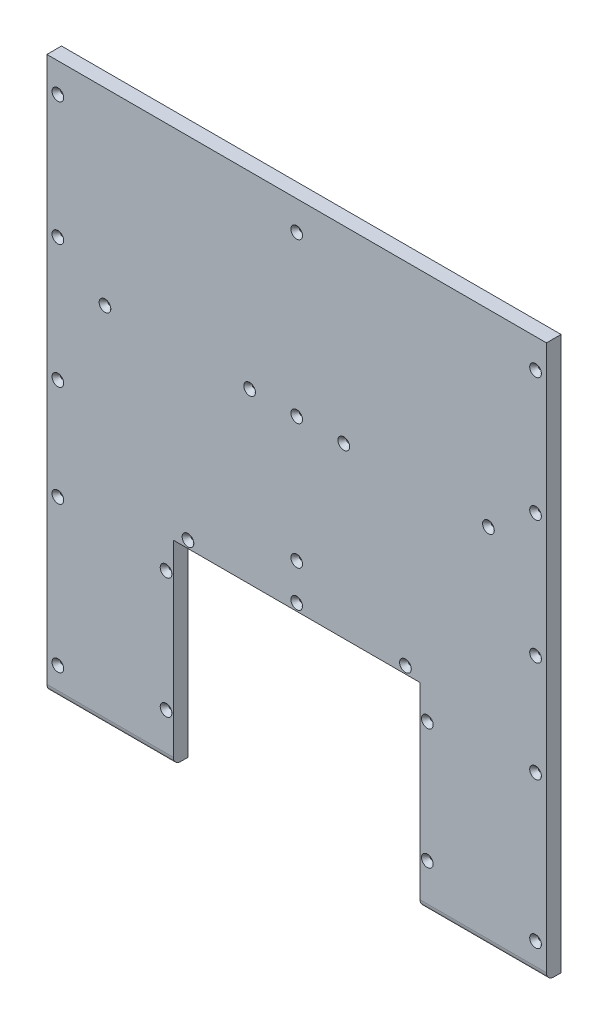
SolidWorks part; units mm, degrees
material "Beech"
ref_plane "Front Plane" through (0, 0, 0) normal (0, 0, 1) x (1, 0, 0)
ref_plane "Top Plane" through (0, 0, 0) normal (0, 1, 0) x (1, 0, 0)
ref_plane "Right Plane" through (0, 0, 0) normal (1, 0, 0) x (0, 0, -1)
sketch "Sketch1" plane through (0, 0, 0) normal (0, 0, 1) x (1, 0, 0)
  line L0 (124.0045, -60.2629) -> (124.0045, 250.6666) construction
  line L1 (16.7045, -230.2629) -> (-93.2955, -230.2629)
  line L2 (16.7045, -60.2629) -> (16.7045, -230.2629)
  line L3 (-93.2955, -230.2629) -> (-93.2955, 250.6666)
  line L16 (341.3045, -230.2629) -> (341.3045, 250.6666)
  line L17 (341.3045, 250.6666) -> (-93.2955, 250.6666)
  line L21 (16.7045, -60.2629) -> (231.3045, -60.2629)
  line L22 (231.3045, -60.2629) -> (231.3045, -230.2629)
  line L23 (231.3045, -230.2629) -> (341.3045, -230.2629)
  dimension "D1" = 434.6
  dimension "D2" = 480.9295
  dimension "D3" = 110
  dimension "D4" = 170
extrude "Boss-Extrude1" add sketch "Sketch1" against normal blind 12.7
fillet "Fillet1" radius 6.35 2 edges at (286.3045, -230.2629, 0) (-38.2955, -230.2629, 0)
hole_wizard "Hole1" positions "Sketch2" profile "Sketch3" legacy end condition through all
sketch "Sketch2" plane through (0, 0, 0) normal (0, 0, 1) x (1, 0, 0)
  line L8 (331.7795, 250.6666) -> (331.7795, -230.2629) construction
  line L9 (341.3045, 250.6666) -> (-93.2955, 250.6666) construction
  line L12 (322.2545, 226.323) -> (322.2545, -204.8629) construction
  line L13 (341.3045, -204.8629) -> (341.3045, 226.323) construction
  line L15 (331.7795, 225.2666) -> (331.7795, 10.2019)
  line L16 (331.7795, 10.2019) -> (331.7795, -204.8629)
  line L17 (133.5295, 86.6832) -> (322.2545, 86.6832) construction
  line L19 (322.2545, 96.2082) -> (133.5295, 96.2082) construction
  line L20 (133.5295, 77.1582) -> (322.2545, 77.1582) construction
  line L21 (133.5295, -47.5629) -> (133.5295, 259.4032) construction
  line L22 (322.2545, 259.4032) -> (322.2545, -217.5629) construction
  line L23 (133.5295, 86.6832) -> (196.4378, 86.6832)
  line L24 (196.4378, 86.6832) -> (259.3461, 86.6832)
  line L25 (259.3461, 86.6832) -> (322.2545, 86.6832)
  line L26 (341.3045, -230.2629) -> (231.3045, -230.2629) construction
  line L27 (237.6545, -60.2629) -> (237.6545, -217.5629) construction
  line L31 (237.6545, -60.2629) -> (237.6545, -112.6962)
  line L32 (237.6545, -112.6962) -> (237.6545, -165.1295)
  line L33 (237.6545, -165.1295) -> (237.6545, -217.5629)
  line L34 (124.0045, 250.6666) -> (124.0045, -47.5629) construction
  line L36 (114.4795, 226.323) -> (114.4795, -49.1129) construction
  line L37 (133.5295, -49.1129) -> (133.5295, 226.323) construction
  line L38 (4.0045, -53.9129) -> (244.0045, -53.9129) construction
  line L40 (4.0045, -47.5629) -> (244.0045, -47.5629) construction
  line L41 (4.0045, -60.2629) -> (244.0045, -60.2629) construction
  line L42 (4.0045, -60.2629) -> (4.0045, -47.5629) construction
  line L43 (244.0045, -47.5629) -> (244.0045, -60.2629) construction
  point P29 (331.7795, -204.8629)
  point P32 (331.7795, 10.2019)
  point P34 (331.7795, 225.2666)
  point P54 (331.7795, 117.7343)
  point P61 (331.7795, -77.8629)
  point P87 (164.9836, 86.6832)
  point P89 (290.8003, 86.6832)
  point P118 (237.6545, -86.4795)
  point P120 (237.6545, -191.3462)
  point P143 (124.0045, 86.6832)
  point P145 (124.0045, 225.2666)
  point P147 (124.0045, -22.1629)
  point P151 (10.3545, -191.3462)
  point P152 (10.3545, -86.4795)
  point P153 (-42.7914, 86.6832)
  point P154 (83.0253, 86.6832)
  point P155 (-83.7705, -77.8629)
  point P156 (-83.7705, 117.7343)
  point P157 (-83.7705, 225.2666)
  point P158 (-83.7705, 10.2019)
  point P159 (-83.7705, -204.8629)
  point P174 (124.0045, -53.9129)
  point P176 (29.4045, -53.9129)
  point P178 (218.6045, -53.9129)
  dimension "D1" = 25.4
  dimension "D2" = 127
  dimension "D3" = 25.4
  dimension "D4" = 25.4
  dimension "D5" = 25.4
  dimension "D6" = 25.4
  dimension "D7" = 25.4
sketch "Sketch3" plane through (218.6045, -53.9129, 0) normal (1, 0, 0) x (0, -1, 0)
  line L0 (0, 0) -> (0, 13.6539)
  line L1 (0, 13.6539) -> (1.5875, 12.7)
  line L2 (1.5875, 12.7) -> (1.5875, 4.0177)
  line L3 (1.5875, 4.0177) -> (5.08, 0)
  line L4 (5.08, 0) -> (0, 0)
  line L5 (0, -14.3089) -> (0, 102.4216) construction
  line L6 (0, 13.6539) -> (-1.5875, 12.7) construction
  line L7 (-1.5875, 4.0177) -> (-5.08, 0) construction
  dimension "Diameter" = 3.175
  dimension "Depth" = 12.7
  dimension "C-Sink Diameter" = 10.16
  dimension "C-Sink Angle" = 82
  dimension "Drill Angle" = 118
hole_wizard "Hole2" positions "Sketch4" profile "Sketch5" legacy
sketch "Sketch4" plane through (124.0045, -215.2871, 0) normal (0, 0, 1) x (1, 0, 0)
  line L1 (0, 465.9538) -> (0, 167.7243) construction
  point P1 (113.65, 128.8076)
  point P3 (113.65, 23.941)
  point P5 (-94.6, 161.3743)
  point P7 (94.6, 161.3743)
  point P9 (0, 161.3743)
  point P11 (0, 193.1243)
  point P13 (0, 440.5538)
  point P15 (0, 301.9704)
  point P17 (40.9792, 301.9704)
  point P19 (166.7958, 301.9704)
  point P21 (207.775, 440.5538)
  point P23 (207.775, 333.0214)
  point P25 (207.775, 225.489)
  point P27 (207.775, 137.4243)
  point P29 (207.775, 10.4243)
  point P33 (-207.775, 10.4243)
  point P34 (-207.775, 137.4243)
  point P35 (-207.775, 225.489)
  point P36 (-207.775, 333.0214)
  point P37 (-207.775, 440.5538)
  point P38 (-166.7958, 301.9704)
  point P39 (-40.9792, 301.9704)
  point P40 (-113.65, 23.941)
  point P41 (-113.65, 128.8076)
sketch "Sketch5" plane through (237.6545, -86.4795, 0) normal (1, 0, 0) x (0, -1, 0)
  line L0 (0, 0) -> (0, 32.7039)
  line L1 (0, 32.7039) -> (1.5875, 31.75)
  line L2 (1.5875, 31.75) -> (1.5875, 4.0177)
  line L3 (1.5875, 4.0177) -> (5.08, 0)
  line L4 (5.08, 0) -> (0, 0)
  line L5 (0, -14.3089) -> (0, 102.4216) construction
  line L6 (0, 32.7039) -> (-1.5875, 31.75) construction
  line L7 (-1.5875, 4.0177) -> (-5.08, 0) construction
  dimension "Diameter" = 3.175
  dimension "Depth" = 31.75
  dimension "C-Sink Diameter" = 10.16
  dimension "C-Sink Angle" = 82
  dimension "Drill Angle" = 118
